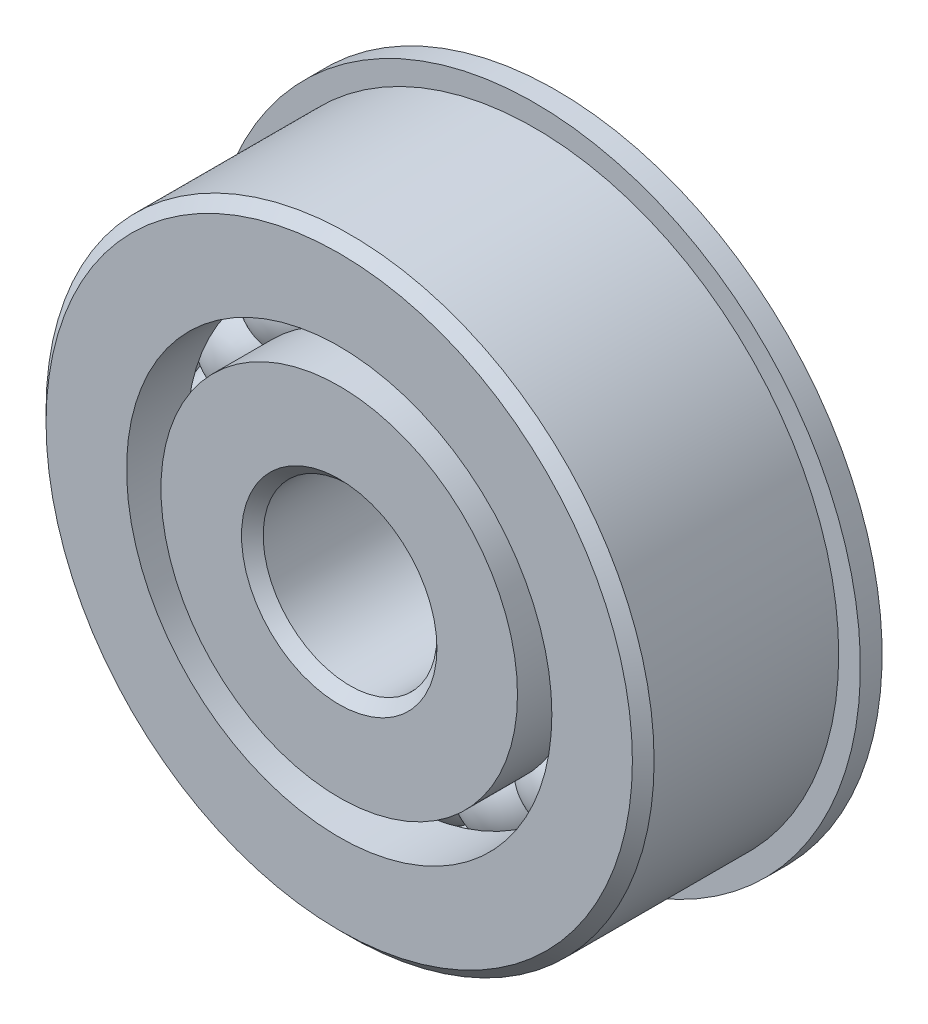
SolidWorks part; units mm, degrees
ref_plane "Front Plane" through (0, 0, 0) normal (0, 0, 1) x (1, 0, 0)
ref_plane "Top Plane" through (0, 0, 0) normal (0, 1, 0) x (1, 0, 0)
ref_plane "Right Plane" through (0, 0, 0) normal (1, 0, 0) x (0, 0, -1)
sketch "Sketch1" plane through (0, 0, 0) normal (1, 0, 0) x (0, 0, -1)
  line L0 (-7.9375, 0) -> (7.9375, 0) construction
  line L1 (0, 22.225) -> (0, -22.225) construction
  line L2 (7.1438, 22.225) -> (-7.1438, 22.225)
  line L3 (-7.1438, 22.225) -> (-7.9375, 21.4312)
  line L4 (-7.9375, 21.4312) -> (-7.9375, 15.5435)
  line L5 (-7.9375, 15.5435) -> (-3.5278, 15.5435)
  line L6 (7.9375, 15.5435) -> (3.5278, 15.5435)
  line L7 (7.9375, 21.4313) -> (7.9375, 15.5435)
  line L8 (7.1438, 22.225) -> (7.9375, 21.4313)
  line L9 (0, 22.225) -> (0, 14.2875) construction
  line L10 (0, 14.2875) -> (0, 6.35) construction
  arc A0 (-3.5278, 15.5435) -> (3.5278, 15.5435) centre (0, 14.2875) cw
  point P14 (0, 6.35)
  dimension "Width" = 15.875
  dimension "OD" = 44.45
  dimension "D1" = 45
  dimension "D2" = 0.7937
  dimension "Shaft Dia" = 12.7
  dimension "D3" = 7.0556
  dimension "D4" = 1.256
revolve "Revolve1" add sketch "Sketch1" angle 360 about L0
sketch "Sketch3" plane through (0, 0, 0) normal (1, 0, 0) x (0, 0, -1)
  line L0 (-7.9375, 13.0315) -> (-3.5278, 13.0315)
  line L1 (0, 22.225) -> (0, -22.225) construction
  line L2 (-7.9375, 21.4312) -> (-7.9375, 15.5435) construction
  line L3 (-7.9375, 13.0315) -> (-7.9375, 7.1437)
  line L4 (-7.1438, 22.225) -> (-7.9375, 21.4312) construction
  line L5 (-7.9375, 7.1437) -> (-7.1438, 6.35)
  line L6 (-7.1438, 6.35) -> (7.1438, 6.35)
  line L7 (7.1438, 22.225) -> (7.1438, -22.225) construction
  line L8 (7.1438, 6.35) -> (7.9375, 7.1437)
  line L9 (7.9375, -21.4313) -> (7.9375, 21.4313) construction
  line L10 (7.9375, 7.1437) -> (7.9375, 13.0315)
  line L11 (7.9375, 13.0315) -> (3.5278, 13.0315)
  line L13 (7.1438, 22.225) -> (7.9375, 21.4313) construction
  arc A0 (3.5278, 15.5435) -> (-3.5278, 15.5435) centre (0, 14.2875) ccw construction
  arc A1 (3.5278, 13.0315) -> (-3.5278, 13.0315) centre (0, 14.2875) cw
revolve "Revolve3" add sketch "Sketch3" angle 360 about L0
sketch "Sketch4" plane through (0, 0, 0) normal (1, 0, 0) x (0, 0, -1)
  line L0 (-3.7447, 14.2875) -> (3.7447, 14.2875)
  arc A2 (-3.7447, 14.2875) -> (3.7447, 14.2875) centre (0, 14.2875) cw
  arc A3 (3.5278, 15.5435) -> (-3.5278, 15.5435) centre (0, 14.2875) ccw construction
revolve "Revolve4" add sketch "Sketch4" angle 360 about L0
ref_axis "Axis1" through (0, 0, -7.9375) along (0, 0, 1)
pattern_circular "CirPattern1" count 16 every 22.5 about axis through (0, 0, -7.9375) along (0, 0, 1) of bodies 104
sketch "Sketch5" plane through (0, 0, 0) normal (1, 0, 0) x (0, 0, -1)
  line L0 (-7.9375, 15.5435) -> (-3.5278, 15.5435) construction
  line L1 (-7.5406, 15.5435) -> (-3.7447, 15.5435)
  line L2 (-7.5406, 15.5435) -> (-7.5406, 13.0315)
  line L3 (-7.5406, 13.0315) -> (-3.7447, 13.0315)
  line L4 (-3.7447, 15.5435) -> (-3.7447, 13.0315)
  line L5 (-7.9375, 13.0315) -> (-3.5278, 13.0315) construction
  line L6 (7.9375, 15.5435) -> (3.5278, 15.5435) construction
  line L7 (7.5406, 15.5435) -> (3.7447, 15.5435)
  line L8 (7.5406, 15.5435) -> (7.5406, 13.0315)
  line L9 (7.5406, 13.0315) -> (3.7447, 13.0315)
  line L10 (3.7447, 15.5435) -> (3.7447, 13.0315)
  line L11 (7.9375, 13.0315) -> (3.5278, 13.0315) construction
  line L12 (-7.1438, 22.225) -> (-7.9375, 21.4312) construction
  point P18 (-7.5406, 21.8281)
revolve "Revolve5" [suppressed] add sketch "Sketch5" angle 360 about L0
sketch "Sketch6" plane through (0, 0, 0) normal (1, 0, 0) x (0, 0, -1)
  line L0 (7.9375, 0) -> (-7.9375, 0) construction
  line L1 (7.9375, 15.5435) -> (6.35, 15.5435)
  line L2 (7.9375, 15.5435) -> (7.9375, 23.8125)
  line L3 (7.9375, 23.8125) -> (6.35, 23.8125)
  line L4 (6.35, 15.5435) -> (6.35, 23.8125)
  dimension "Th" = 1.5875
  dimension "Flange OD" = 47.625
revolve "Revolve6" add sketch "Sketch6" angle 360 about L0
equation "\"D2@Sketch1\" = \"Width@Sketch1\"*.05"
equation "\"D3@Sketch1\" = \"Width@Sketch1\"/2.25"
equation "\"D4@Sketch1\" = (((\"OD@Sketch1\"-\"Width@Sketch1\")/2)/3.25)/3.5"
equation "\"D2@CirPattern1\" = 360/\"Balls@CirPattern1\""
